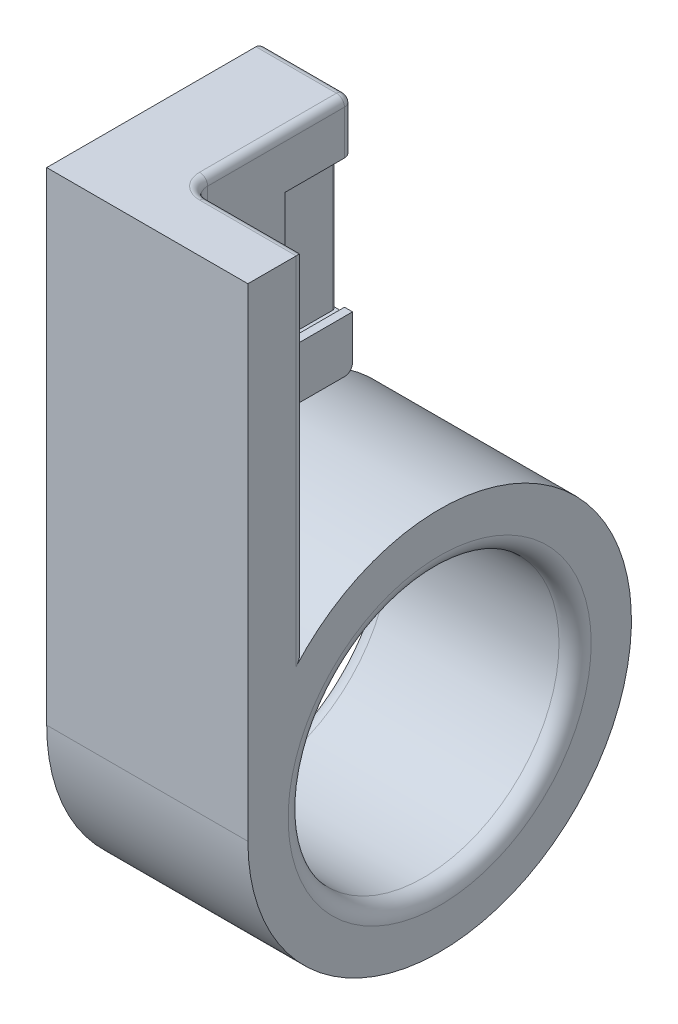
SolidWorks part; units mm, degrees
ref_plane "Front Plane" through (0, 0, 0) normal (0, 0, 1) x (1, 0, 0)
ref_plane "Top Plane" through (0, 0, 0) normal (0, 1, 0) x (1, 0, 0)
ref_plane "Right Plane" through (0, 0, 0) normal (1, 0, 0) x (0, 0, -1)
sketch "Sketch1" plane through (0, 0, 0) normal (1, 0, 0) x (0, 0, -1)
  circle A0 centre (0, 0) radius 16.8275
  circle A1 centre (0, 0) radius 23.8275
  dimension "D1" = 33.655
  dimension "D2" = 7
extrude "Boss-Extrude1" add sketch "Sketch1" along normal blind 25 contours A1 | A0
sketch "Sketch2" plane through (0, 0, 0) normal (0, 1, 0) x (1, 0, 0)
  line L0 (25, -23.8275) -> (25, 23.8275) construction
  line L1 (0, -23.8275) -> (25, -23.8275)
  line L2 (0, -23.8275) -> (0, -16.8275)
  line L3 (0, -16.8275) -> (25, -16.8275)
  line L4 (25, -23.8275) -> (25, -16.8275)
  line L5 (25, -16.8275) -> (25, 16.8275) construction
  point P7 (0, 0)
  point P10 (0, 0)
extrude "Boss-Extrude2" add sketch "Sketch2" along normal blind 60
sketch "Sketch3" plane through (0, 0, 16.8275) normal (0, 0, -1) x (-1, 0, 0)
  line L1 (0, 60) -> (-11, 60)
  line L2 (0, 60) -> (0, 30)
  line L3 (0, 30) -> (-11, 30)
  line L4 (-11, 60) -> (-11, 30)
  dimension "D1" = 11
  dimension "D2" = 30
extrude "Boss-Extrude3" add sketch "Sketch3" along normal blind 20
sketch "Sketch4" plane through (11, 0, 0) normal (1, 0, 0) x (0, 0, -1)
  line L0 (3.1725, 60) -> (3.1725, 30) construction
  line L1 (3.1725, 45) -> (-16.8275, 45)
  line L2 (-16.8275, 60) -> (-16.8275, 30) construction
  line L4 (-5.2275, 53.525) -> (3.1725, 53.525)
  line L5 (-5.2275, 53.525) -> (-5.2275, 36.475)
  line L6 (-5.2275, 36.475) -> (3.1725, 36.475)
  line L7 (3.1725, 53.525) -> (3.1725, 36.475)
  line L8 (-5.2275, 53.525) -> (3.1725, 36.475) construction
  line L9 (-5.2275, 36.475) -> (3.1725, 53.525) construction
  point P8 (-1.0275, 45)
  line M8 (3.1725, 30) -> (3.1725, 60)
  dimension "D1" = 17.05
  dimension "D2" = 8.4
extrude "Cut-Extrude1" cut sketch "Sketch4" against normal blind 1 contours L5 L6 L1 M8 | L4 L5 L1 M8 region at (11, 40.7375, 1.0275) region at (11, 49.2625, 1.0275)
sketch "Sketch5" plane through (10, 0, 0) normal (1, 0, 0) x (0, 0, -1)
  line L0 (3.1725, 53.525) -> (3.1725, 36.475) construction
  line L1 (3.1725, 45) -> (-5.2275, 45) construction
  line L2 (-5.2275, 53.525) -> (-5.2275, 36.475) construction
  line L4 (-5.8275, 54.125) -> (3.1725, 54.125)
  line L5 (-5.8275, 54.125) -> (-5.8275, 35.875)
  line L6 (-5.8275, 35.875) -> (3.1725, 35.875)
  line L7 (3.1725, 54.125) -> (3.1725, 35.875)
  line L8 (-5.8275, 54.125) -> (3.1725, 35.875) construction
  line L9 (-5.8275, 35.875) -> (3.1725, 54.125) construction
  point P8 (-1.3275, 45)
  dimension "D1" = 18.25
  dimension "D2" = 9
extrude "Cut-Extrude2" cut sketch "Sketch5" against normal blind 1
fillet "Fillet1" radius 0.5 1 edges at (9, 45, -3.1725)
fillet "Fillet2" radius 1 3 edges at (5.5, 30, -3.1725) (0, 45, -3.1725) (5.5, 60, -3.1725)
fillet "Fillet3" radius 2 2 edges at (25, 0, -16.8275) (0, 0, -16.8275)
fillet "Fillet4" radius 2 1 edges at (11, 45, 16.8275)
fillet "Fillet6" radius 1 6 edges at (11, 56.2625, -3.1725) (11, 59.7071, -2.8796) (11, 60, 6.3275) (11.5858, 60, 16.2417) (19, 60, 16.8275) (25, 38.4348, 16.8275)
